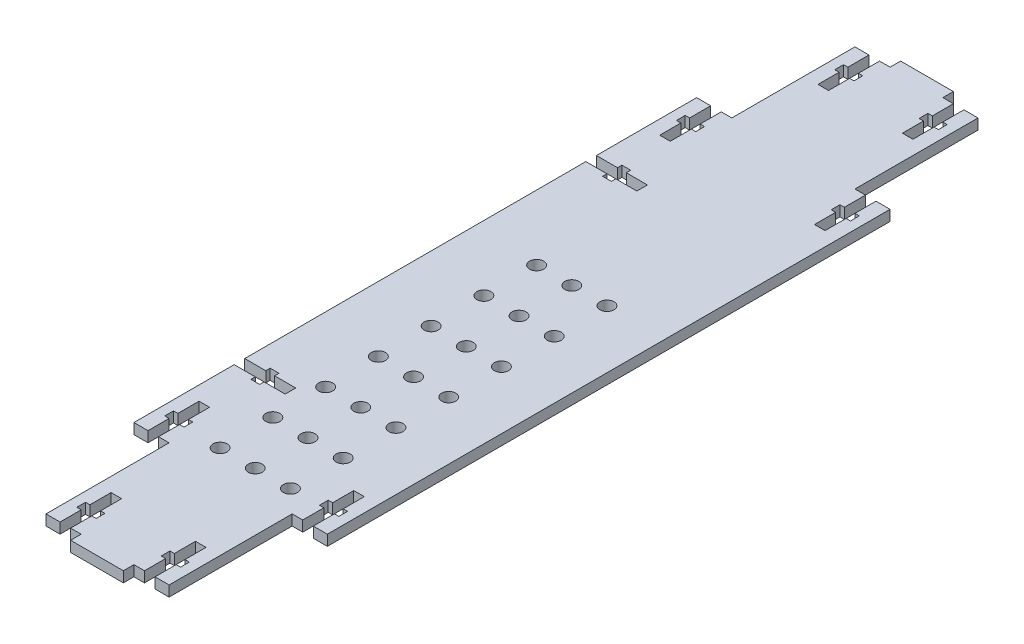
SolidWorks part; units mm, degrees
ref_plane "Спереди" through (0, 0, 0) normal (0, 0, 1) x (1, 0, 0)
ref_plane "Сверху" through (0, 0, 0) normal (0, 1, 0) x (1, 0, 0)
ref_plane "Справа" through (0, 0, 0) normal (1, 0, 0) x (0, 0, -1)
sketch "Эскиз1" plane through (0, 0, 0) normal (0, 1, 0) x (1, 0, 0)
  line L1 (-27.5, -80) -> (27.5, -80)
  line L2 (-27.5, -80) -> (-27.5, 80)
  line L3 (-27.5, 80) -> (27.5, 80)
  line L4 (27.5, -80) -> (27.5, 80)
  line L5 (-27.5, -80) -> (27.5, 80) construction
  line L6 (-27.5, 80) -> (27.5, -80) construction
  point P0 (0, 0)
  dimension "D1" = 55
  dimension "D2" = 160
extrude "Бобышка-Вытянуть1" add sketch "Эскиз1" along normal blind 3
sketch "Эскиз2" plane through (0, 0, -80) normal (0, 0, -1) x (-1, 0, 0)
  line L0 (-27.5, 0) -> (27.5, 0) construction
  line L1 (-17.5, 0) -> (17.5, 0)
  line L2 (-17.5, 0) -> (-17.5, 3)
  line L3 (-17.5, 3) -> (17.5, 3)
  line L4 (17.5, 0) -> (17.5, 3)
  line L5 (-27.5, 3) -> (27.5, 3) construction
  point P8 (0, 3)
  dimension "D1" = 35
  dimension "D2" = 27.5
extrude "Бобышка-Вытянуть2" add sketch "Эскиз2" along normal blind 35 and the other way blind 195
sketch "Эскиз3" plane through (0, 0, -115) normal (0, 0, -1) x (-1, 0, 0)
  line L0 (-17.5, 0) -> (17.5, 0) construction
  line L1 (-7.5, 0) -> (7.5, 0)
  line L2 (-7.5, 0) -> (-7.5, 3)
  line L3 (-7.5, 3) -> (7.5, 3)
  line L4 (7.5, 0) -> (7.5, 3)
  line L5 (17.5, 3) -> (-17.5, 3) construction
  point P8 (0, 0)
  dimension "D1" = 15
  dimension "D2" = 27.5
extrude "Бобышка-Вытянуть3" add sketch "Эскиз3" along normal blind 3 and the other way blind 233
sketch "Эскиз4" plane through (0, 3, 0) normal (0, 1, 0) x (1, 0, 0)
  line L0 (-23.5, 80) -> (-23.5, 74)
  line L1 (-13.5, 115) -> (-13.5, 109)
  line L2 (-23.5, 74) -> (-24.75, 74)
  line L3 (-24.75, 74) -> (-24.75, 71.5)
  line L4 (-24.75, 71.5) -> (-23.5, 71.5)
  line L5 (-23.5, 71.5) -> (-23.5, 65.5)
  line L6 (-23.5, 65.5) -> (-20.5, 65.5)
  line L7 (-20.5, 65.5) -> (-20.5, 71.5)
  line L8 (-20.5, 71.5) -> (-19.25, 71.5)
  line L9 (-19.25, 71.5) -> (-19.25, 74)
  line L10 (-19.25, 74) -> (-20.5, 74)
  line L11 (-20.5, 74) -> (-20.5, 80)
  line L12 (-13.5, 109) -> (-14.75, 109)
  line L13 (-20.5, 80) -> (-23.5, 80)
  line L14 (-14.75, 109) -> (-14.75, 106.5)
  line L15 (-14.75, 106.5) -> (-13.5, 106.5)
  line L16 (-13.5, 106.5) -> (-13.5, 100.5)
  line L17 (-13.5, 100.5) -> (-10.5, 100.5)
  line L18 (-10.5, 100.5) -> (-10.5, 106.5)
  line L19 (-10.5, 106.5) -> (-9.25, 106.5)
  line L20 (-9.25, 106.5) -> (-9.25, 109)
  line L21 (-9.25, 109) -> (-10.5, 109)
  line L22 (-10.5, 109) -> (-10.5, 115)
  line L23 (-10.5, 115) -> (-13.5, 115)
  line L24 (-17.5, 80) -> (-27.5, 80) construction
  line L25 (-17.5, 115) -> (-7.5, 115) construction
  line L26 (0, 118) -> (0, 75.6534) construction
  line L27 (-7.5, 118) -> (7.5, 118) construction
  line L28 (-27.5, 0) -> (22.9967, 0) construction
  line L29 (-27.5, 80) -> (-27.5, -80) construction
  line L30 (10.5, 115) -> (13.5, 115)
  line L31 (10.5, 109) -> (10.5, 115)
  line L32 (9.25, 109) -> (10.5, 109)
  line L33 (9.25, 106.5) -> (9.25, 109)
  line L34 (10.5, 106.5) -> (9.25, 106.5)
  line L35 (10.5, 100.5) -> (10.5, 106.5)
  line L36 (13.5, 100.5) -> (10.5, 100.5)
  line L37 (13.5, 106.5) -> (13.5, 100.5)
  line L38 (14.75, 106.5) -> (13.5, 106.5)
  line L39 (14.75, 109) -> (14.75, 106.5)
  line L40 (20.5, 80) -> (23.5, 80)
  line L41 (13.5, 109) -> (14.75, 109)
  line L42 (20.5, 74) -> (20.5, 80)
  line L43 (19.25, 74) -> (20.5, 74)
  line L44 (19.25, 71.5) -> (19.25, 74)
  line L45 (20.5, 71.5) -> (19.25, 71.5)
  line L46 (20.5, 65.5) -> (20.5, 71.5)
  line L47 (23.5, 65.5) -> (20.5, 65.5)
  line L48 (23.5, 71.5) -> (23.5, 65.5)
  line L49 (24.75, 71.5) -> (23.5, 71.5)
  line L50 (24.75, 74) -> (24.75, 71.5)
  line L51 (23.5, 74) -> (24.75, 74)
  line L52 (13.5, 115) -> (13.5, 109)
  line L53 (23.5, 80) -> (23.5, 74)
  line L54 (-10.5, -115) -> (-13.5, -115)
  line L55 (-10.5, -109) -> (-10.5, -115)
  line L56 (-9.25, -109) -> (-10.5, -109)
  line L57 (-9.25, -106.5) -> (-9.25, -109)
  line L58 (-10.5, -106.5) -> (-9.25, -106.5)
  line L59 (-10.5, -100.5) -> (-10.5, -106.5)
  line L60 (-13.5, -100.5) -> (-10.5, -100.5)
  line L61 (-13.5, -106.5) -> (-13.5, -100.5)
  line L62 (-14.75, -106.5) -> (-13.5, -106.5)
  line L63 (-14.75, -109) -> (-14.75, -106.5)
  line L64 (-13.5, -109) -> (-14.75, -109)
  line L65 (-13.5, -115) -> (-13.5, -109)
  line L66 (13.5, -115) -> (13.5, -109)
  line L67 (13.5, -109) -> (14.75, -109)
  line L68 (14.75, -109) -> (14.75, -106.5)
  line L69 (14.75, -106.5) -> (13.5, -106.5)
  line L70 (13.5, -106.5) -> (13.5, -100.5)
  line L71 (13.5, -100.5) -> (10.5, -100.5)
  line L72 (10.5, -100.5) -> (10.5, -106.5)
  line L73 (10.5, -106.5) -> (9.25, -106.5)
  line L74 (9.25, -106.5) -> (9.25, -109)
  line L75 (9.25, -109) -> (10.5, -109)
  line L76 (10.5, -109) -> (10.5, -115)
  line L77 (10.5, -115) -> (13.5, -115)
  line L78 (-20.5, -80) -> (-23.5, -80)
  line L79 (-20.5, -74) -> (-20.5, -80)
  line L80 (-19.25, -74) -> (-20.5, -74)
  line L81 (-19.25, -71.5) -> (-19.25, -74)
  line L82 (-20.5, -71.5) -> (-19.25, -71.5)
  line L83 (-20.5, -65.5) -> (-20.5, -71.5)
  line L84 (-23.5, -65.5) -> (-20.5, -65.5)
  line L85 (-23.5, -71.5) -> (-23.5, -65.5)
  line L86 (-24.75, -71.5) -> (-23.5, -71.5)
  line L87 (-24.75, -74) -> (-24.75, -71.5)
  line L88 (-23.5, -74) -> (-24.75, -74)
  line L89 (-23.5, -80) -> (-23.5, -74)
  line L90 (23.5, -80) -> (23.5, -74)
  line L91 (23.5, -74) -> (24.75, -74)
  line L92 (24.75, -74) -> (24.75, -71.5)
  line L93 (24.75, -71.5) -> (23.5, -71.5)
  line L94 (23.5, -71.5) -> (23.5, -65.5)
  line L95 (23.5, -65.5) -> (20.5, -65.5)
  line L96 (20.5, -65.5) -> (20.5, -71.5)
  line L97 (20.5, -71.5) -> (19.25, -71.5)
  line L98 (19.25, -71.5) -> (19.25, -74)
  line L99 (19.25, -74) -> (20.5, -74)
  line L100 (20.5, -74) -> (20.5, -80)
  line L101 (20.5, -80) -> (23.5, -80)
  point P29 (-22, 80)
  point P112 (-12, 115)
  dimension "D1" = 3
  dimension "D2" = 5.5
  dimension "D3" = 6
  dimension "D4" = 2.5
  dimension "D5" = 3
  dimension "D6" = 5.5
  dimension "D7" = 6
  dimension "D8" = 2.5
  dimension "D9" = 4.5
  dimension "D10" = 4
  dimension "D11" = 4.5
extrude "Вырез-Вытянуть1" cut sketch "Эскиз4" against normal blind 3
sketch "Эскиз5" plane through (0, 3, 0) normal (0, 1, 0) x (1, 0, 0)
  line L0 (-27.5, 51.5) -> (-21.5, 51.5)
  line L1 (-21.5, 51.5) -> (-21.5, 52.75)
  line L2 (-21.5, 52.75) -> (-19, 52.75)
  line L3 (-19, 52.75) -> (-19, 51.5)
  line L4 (-19, 51.5) -> (-13, 51.5)
  line L5 (-13, 51.5) -> (-13, 48.5)
  line L6 (-13, 48.5) -> (-19, 48.5)
  line L7 (-19, 48.5) -> (-19, 47.25)
  line L8 (-19, 47.25) -> (-21.5, 47.25)
  line L9 (-21.5, 47.25) -> (-21.5, 48.5)
  line L10 (-21.5, 48.5) -> (-27.5, 48.5)
  line L11 (-27.5, 48.5) -> (-27.5, 51.5)
  line L12 (-27.5, 80) -> (-27.5, -80) construction
  line L13 (-27.5, 0) -> (-6.9327, 0) construction
  line L14 (-27.5, -48.5) -> (-27.5, -51.5)
  line L15 (-21.5, -48.5) -> (-27.5, -48.5)
  line L16 (-21.5, -47.25) -> (-21.5, -48.5)
  line L17 (-19, -47.25) -> (-21.5, -47.25)
  line L18 (-19, -48.5) -> (-19, -47.25)
  line L19 (-13, -48.5) -> (-19, -48.5)
  line L20 (-13, -51.5) -> (-13, -48.5)
  line L21 (-19, -51.5) -> (-13, -51.5)
  line L22 (-19, -52.75) -> (-19, -51.5)
  line L23 (-21.5, -52.75) -> (-19, -52.75)
  line L24 (-21.5, -51.5) -> (-21.5, -52.75)
  line L25 (-27.5, -51.5) -> (-21.5, -51.5)
  point P30 (-27.5, 50)
  dimension "D1" = 3
  dimension "D2" = 6
  dimension "D3" = 2.5
  dimension "D4" = 5.5
  dimension "D5" = 50
extrude "Вырез-Вытянуть2" cut sketch "Эскиз5" against normal blind 3
sketch "Эскиз6" plane through (0, 3, 0) normal (0, 1, 0) x (1, 0, 0)
  circle A0 centre (-9, -74) radius 2
  point P2 (0, 0)
  dimension "D1" = 4
  dimension "D2" = 4
  dimension "D3" = 6
extrude "Вырез-Вытянуть3" cut sketch "Эскиз6" against normal blind 10
pattern_linear "Линейный массив1" count 7 spacing 15 along (0, 0, -1) count 3 spacing 10 along (1, 0, 0) of "Вырез-Вытянуть3"
